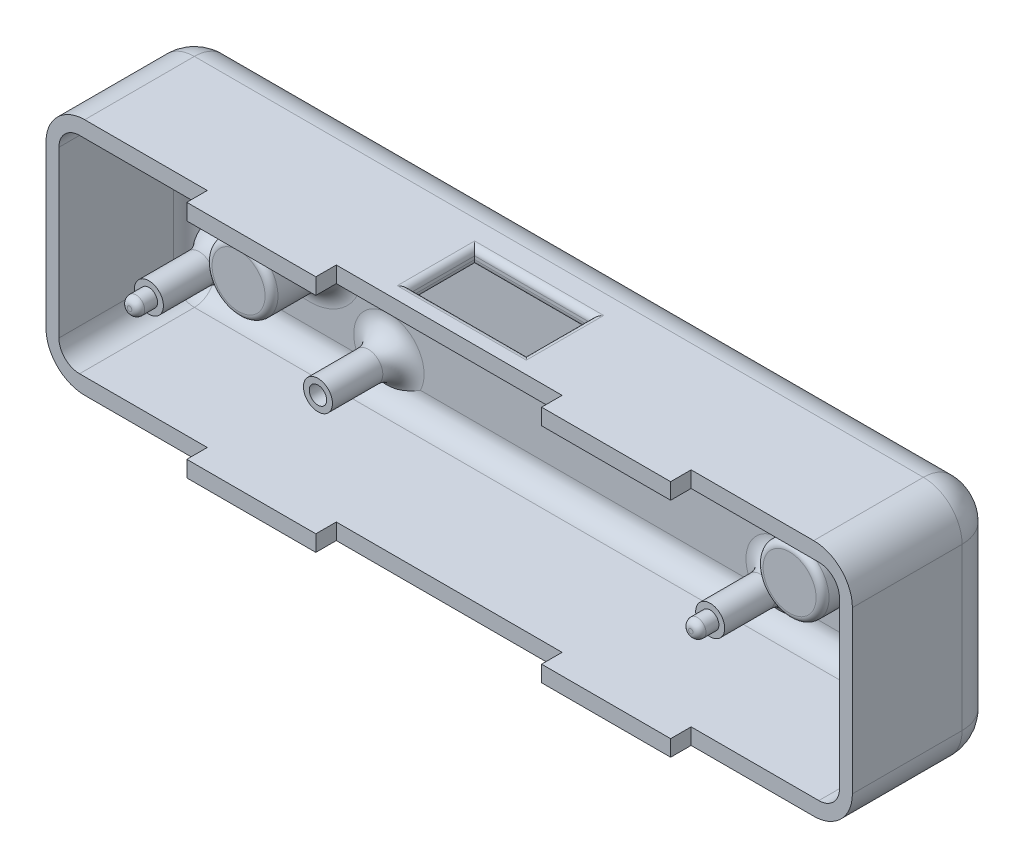
SolidWorks part; units mm, degrees
ref_plane "Front" through (0, 0, 0) normal (0, 0, 1) x (1, 0, 0)
ref_plane "Top" through (0, 0, 0) normal (0, 1, 0) x (1, 0, 0)
ref_plane "Right" through (0, 0, 0) normal (1, 0, 0) x (0, 0, -1)
sketch "Sketch1" plane through (0, 0, 0) normal (0, 0, 1) x (1, 0, 0)
  line L1 (-62.5, -18.5) -> (62.5, -18.5)
  line L2 (-62.5, -18.5) -> (-62.5, 18.5)
  line L3 (-62.5, 18.5) -> (62.5, 18.5)
  line L4 (62.5, -18.5) -> (62.5, 18.5)
  line L5 (-62.5, -18.5) -> (62.5, 18.5) construction
  line L6 (-62.5, 18.5) -> (62.5, -18.5) construction
  point P0 (0, 0)
  dimension "D1" = 37
  dimension "D2" = 125
extrude "Boss-Extrude1" add sketch "Sketch1" along normal blind 2 contours L3 L4 L1 L2
sketch "Sketch2" plane through (0, 0, 2) normal (0, 0, 1) x (1, 0, 0)
  line L0 (-60.5, 0) -> (60.5, 0) construction
  line L1 (60.5, -18.5) -> (-60.5, -18.5)
  line L2 (0, 0) -> (0, 18.5) construction
  line L3 (-62.5, 18.5) -> (62.5, 18.5) construction
  line L4 (-62.5, -18.5) -> (62.5, -18.5) construction
  line L5 (62.5, 18.5) -> (60.5, 18.5)
  line L6 (62.5, 18.5) -> (62.5, -18.5)
  line L7 (62.5, -18.5) -> (60.5, -18.5)
  line L8 (60.5, 16) -> (60.5, -16)
  line L9 (-62.5, -18.5) -> (-60.5, -18.5)
  line L10 (-60.5, 16) -> (-60.5, -16)
  line L11 (-62.5, 18.5) -> (-60.5, 18.5)
  line L12 (-62.5, 18.5) -> (-62.5, -18.5)
  line L13 (-60.5, -16) -> (60.5, -16)
  line L14 (-60.5, 16) -> (60.5, 16)
  line L15 (60.5, 18.5) -> (-60.5, 18.5)
  point P4 (0, 0)
  point P21 (0, -16)
  dimension "D1" = 121
  dimension "D3" = 2.5
extrude "Boss-Extrude2" add sketch "Sketch2" along normal blind 21
sketch "Sketch4" plane through (0, 0, 0) normal (0, 0, -1) x (-1, 0, 0)
  line L0 (26.7, -12.1572) -> (26.7, 12.1573) construction
  line L1 (-26.7, -14.2) -> (-26.7, 14.2) construction
  line L2 (26.7, -12.1572) -> (26.7, 12.1573) construction
  line L3 (-26.7, -14.2) -> (-26.7, 14.2) construction
  circle A0 centre (-42.7653, 1) radius 5.1095 construction
  circle A1 centre (-42.7653, 1) radius 5.1095 construction
  circle A2 centre (42.6527, -1.2074) radius 5.1095 construction
  circle A3 centre (42.6527, -1.2074) radius 5.1095 construction
  circle A4 centre (-30.4553, -10.18) radius 1.5 construction
  circle A5 centre (-30.4553, 10.18) radius 1.5 construction
  circle A6 centre (-56.6653, 10.18) radius 1.5 construction
  circle A7 centre (-56.6653, -10.18) radius 1.5 construction
  circle A8 centre (56.5527, -10.3874) radius 1.5 construction
  circle A9 centre (56.5527, 9.9726) radius 1.5 construction
  circle A10 centre (30.3427, 9.9726) radius 1.5 construction
  circle A11 centre (30.3427, -10.3874) radius 1.5 construction
  circle A12 centre (-30.4553, -10.18) radius 1.5 construction
  circle A13 centre (-30.4553, 10.18) radius 1.5 construction
  circle A14 centre (-56.6653, 10.18) radius 1.5 construction
  circle A15 centre (-56.6653, -10.18) radius 1.5 construction
  circle A16 centre (56.5527, -10.3874) radius 1.5 construction
  circle A17 centre (56.5527, 9.9726) radius 1.5 construction
  circle A18 centre (30.3427, 9.9726) radius 1.5 construction
  circle A19 centre (30.3427, -10.3874) radius 1.5 construction
sketch "Sketch5" plane through (0, 0, 2) normal (0, 0, 1) x (1, 0, 0)
  circle A0 centre (-42.6527, -1.2074) radius 5.1095 construction
  circle A1 centre (42.7653, 1) radius 5.1095 construction
  circle A2 centre (-42.6527, -1.2074) radius 5.1095
  circle A3 centre (42.7653, 1) radius 5.1095
extrude "Boss-Extrude4" add sketch "Sketch5" along normal blind 11
sketch "Sketch6" plane through (0, 0, 2) normal (0, 0, 1) x (1, 0, 0)
  circle A8 centre (-30.3427, 9.9726) radius 1.35
  circle A9 centre (-56.5527, 9.9726) radius 1.35
  circle A10 centre (-56.5527, -10.3874) radius 1.35
  circle A11 centre (-30.3427, -10.3874) radius 1.35
  circle A12 centre (56.6653, 10.18) radius 1.35
  circle A13 centre (30.4553, 10.18) radius 1.35
  circle A14 centre (30.4553, -10.18) radius 1.35
  circle A15 centre (56.6653, -10.18) radius 1.35
  dimension "D1" = 2.7
  dimension "D2" = 2.7
  dimension "D3" = 2.7
  dimension "D4" = 2.7
  dimension "D5" = 2.7
  dimension "D6" = 2.7
  dimension "D7" = 2.7
  dimension "D8" = 2.7
extrude "Boss-Extrude5" add sketch "Sketch6" along normal blind 14
sketch "Sketch7" plane through (0, 0, 2) normal (0, 0, 1) x (1, 0, 0)
  circle A0 centre (56.6653, -10.18) radius 2.25
  circle A1 centre (30.4553, -10.18) radius 2.25
  circle A2 centre (30.4553, 10.18) radius 2.25
  circle A3 centre (56.6653, 10.18) radius 2.25
  circle A4 centre (-30.3427, 9.9726) radius 2.25
  circle A5 centre (-30.3427, -10.3874) radius 2.25
  circle A6 centre (-56.5527, -10.3874) radius 2.25
  circle A7 centre (-56.5527, 9.9726) radius 2.25
  dimension "D7" = 4.5
  dimension "D1" = 4.5
  dimension "D2" = 4.5
  dimension "D3" = 4.5
  dimension "D4" = 4.5
  dimension "D5" = 4.5
  dimension "D6" = 4.5
  dimension "D8" = 4.5
extrude "Boss-Extrude6" add sketch "Sketch7" along normal blind 11
sketch "Sketch9" plane through (0, 18.5, 0) normal (0, 1, 0) x (1, 0, 0)
  line L0 (0, 0) -> (0, -23) construction
  line L1 (-62.5, 0) -> (62.5, 0) construction
  line L2 (62.5, -23) -> (-62.5, -23) construction
  line L4 (9, -10.0539) -> (-9, -10.0539)
  line L5 (9, -10.0539) -> (9, -20.0539)
  line L6 (9, -20.0539) -> (-9, -20.0539)
  line L7 (-9, -10.0539) -> (-9, -20.0539)
  line L8 (9, -10.0539) -> (-9, -20.0539) construction
  line L9 (9, -20.0539) -> (-9, -10.0539) construction
  point P6 (0, -15.0539)
  dimension "D1" = 18
  dimension "D2" = 10
extrude "Cut-Extrude1" cut sketch "Sketch9" against normal up to next
sketch "Sketch10" plane through (0, 0, 16) normal (0, 0, 1) x (1, 0, 0)
  circle A1 centre (30.4553, 10.18) radius 1.35
  circle A2 centre (30.4553, 10.18) radius 1.35
  circle A3 centre (-30.3427, -10.3874) radius 1.35
  circle A4 centre (-30.3427, -10.3874) radius 1.35
  dimension "D1" = 0
  dimension "D2" = 0
extrude "Cut-Extrude2" cut sketch "Sketch10" against normal blind 12
fillet "Fillet1" radius 3.2 18 edges at (60.5, -16, 12.5) (60.5, 16, 12.5) (-60.5, -16, 12.5) (-60.5, 16, 12.5) (28.2053, -10.18, 2) (28.2053, 10.18, 2) (37.6558, 1, 2) (60.5, 0, 2) (54.4153, 10.18, 2) (54.4153, -10.18, 2) (0, -16, 2) (-60.5, 0, 2) (0, 16, 2) (-32.5927, -10.3874, 2) (-47.7622, -1.2074, 2) (-58.8027, -10.3874, 2) (-58.8027, 9.9726, 2) (-32.5927, 9.9726, 2)
fillet "Fillet2" radius 1 16 edges at (47.8748, 1, 13) (-37.5432, -1.2074, 13) (9, 16, 15.0539) (0, 16, 20.0539) (-9, 16, 15.0539) (0, 16, 10.0539) (0, 18.5, 20.0539) (9, 18.5, 15.0539) (-9, 18.5, 15.0539) (0, 18.5, 10.0539) (58.0153, -10.18, 16) (58.0153, 10.18, 16) (31.8053, -10.18, 16) (-55.2027, -10.3874, 16) (-28.9927, 9.9726, 16) (-55.2027, 9.9726, 16)
fillet "Fillet3" radius 6 8 edges at (0, 18.5, 0) (62.5, 0, 0) (62.5, -18.5, 11.5) (62.5, 18.5, 11.5) (-62.5, -18.5, 11.5) (0, -18.5, 0) (-62.5, 0, 0) (-62.5, 18.5, 11.5)
sketch "Sketch11" plane through (0, 0, 23) normal (0, 0, 1) x (1, 0, 0)
  line L0 (-37.5, 16) -> (-37.5, 18.5)
  line L1 (57.3, 16) -> (-57.3, 16) construction
  line L2 (56.5, 18.5) -> (-56.5, 18.5) construction
  line L3 (-62.5, 12.5) -> (-62.5, -12.5) construction
  line L4 (-37.5, 18.5) -> (-17.5, 18.5)
  line L5 (-17.5, 18.5) -> (-17.5, 16)
  line L6 (-57.3, 16) -> (57.3, 16) construction
  line L7 (-17.5, 16) -> (-37.5, 16)
  line L8 (0, 0) -> (0, 18.5) construction
  line L9 (0, 0) -> (-62.5, 0) construction
  line L10 (-17.5, -16) -> (-37.5, -16)
  line L11 (-17.5, -18.5) -> (-17.5, -16)
  line L12 (-37.5, -18.5) -> (-17.5, -18.5)
  line L13 (-37.5, -16) -> (-37.5, -18.5)
  line L14 (17.5, 16) -> (37.5, 16)
  line L15 (17.5, 18.5) -> (17.5, 16)
  line L16 (37.5, 18.5) -> (17.5, 18.5)
  line L17 (37.5, 16) -> (37.5, 18.5)
  line L18 (37.5, -16) -> (37.5, -18.5)
  line L19 (37.5, -18.5) -> (17.5, -18.5)
  line L20 (17.5, -18.5) -> (17.5, -16)
  line L21 (17.5, -16) -> (37.5, -16)
  dimension "D1" = 25
  dimension "D2" = 20
extrude "Boss-Extrude7" add sketch "Sketch11" along normal blind 3.175
equation "\"3m anchor\"= 4.5mm"
equation "\"D7@Sketch7\"= \"3m anchor\""
equation "\"D1@Sketch7\"=\"3m anchor\""
equation "\"D2@Sketch7\"= \"3m anchor\""
equation "\"D3@Sketch7\"=\"3m anchor\""
equation "\"D4@Sketch7\"=\"3m anchor\""
equation "\"D5@Sketch7\"=\"3m anchor\""
equation "\"D6@Sketch7\"=\"3m anchor\""
equation "\"D8@Sketch7\"=\"3m anchor\""
equation "\"joystick holder\"= 2.7"
equation "\"D1@Sketch6\"=\"joystick holder\""
equation "\"D2@Sketch6\"=\"joystick holder\""
equation "\"D3@Sketch6\"=\"joystick holder\""
equation "\"D4@Sketch6\"=\"joystick holder\""
equation "\"D5@Sketch6\"=\"joystick holder\""
equation "\"D6@Sketch6\"=\"joystick holder\""
equation "\"D7@Sketch6\"=\"joystick holder\""
equation "\"D8@Sketch6\"=\"joystick holder\""
